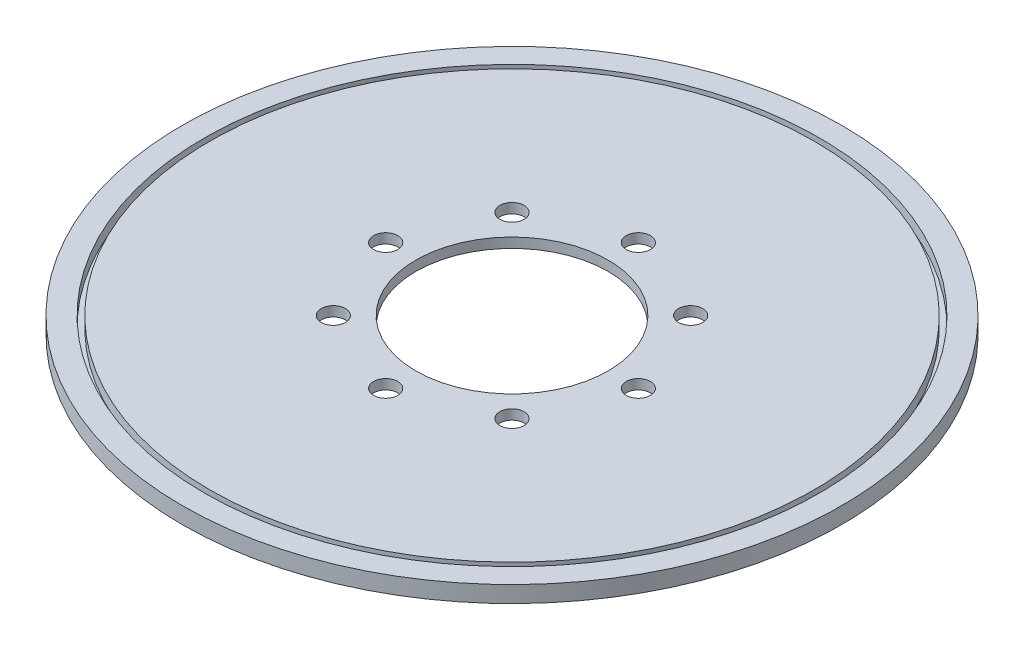
SolidWorks part; units mm, degrees
ref_plane "Front Plane" through (0, 0, 0) normal (0, 0, 1) x (1, 0, 0)
ref_plane "Top Plane" through (0, 0, 0) normal (0, 1, 0) x (1, 0, 0)
ref_plane "Right Plane" through (0, 0, 0) normal (1, 0, 0) x (0, 0, -1)
sketch "Sketch1" plane through (0, 0, 0) normal (0, 1, 0) x (1, 0, 0)
  circle A0 centre (0, 0) radius 300
  point P0 (0, 0)
  dimension "D1" = 600
extrude "plate" add sketch "Sketch1" along normal blind 15
sketch "Sketch2" plane through (0, 15, 0) normal (0, 1, 0) x (1, 0, 0)
  circle A0 centre (0, 0) radius 87.5
  dimension "D1" = 175
extrude "bearing-hole" cut sketch "Sketch2" against normal through all
sketch "Sketch4" plane through (0, 15, 0) normal (0, 1, 0) x (1, 0, 0)
  circle A0 centre (0, 0) radius 280
  circle A1 centre (0, 0) radius 275
  point P0 (0, 0)
  point P6 (0, 0)
  dimension "D1" = 560
  dimension "D2" = 550
extrude "Cut-Extrude3" cut sketch "Sketch4" against normal blind 10
sketch "Sketch5" plane through (0, 0, 0) normal (0, -1, 0) x (1, 0, 0)
  circle A0 centre (0, 0) radius 135
  dimension "D1" = 270
extrude "Cut-Extrude4" cut sketch "Sketch5" against normal blind 6
sketch "Sketch6" plane through (0, 6, 0) normal (0, -1, 0) x (1, 0, 0)
  circle A0 centre (0, 115) radius 6
  circle A1 centre (81.3173, 81.3173) radius 6
  circle A2 centre (115, 0) radius 6
  circle A3 centre (81.3173, -81.3173) radius 6
  circle A4 centre (0, -115) radius 6
  circle A5 centre (-81.3173, -81.3173) radius 6
  circle A6 centre (-115, 0) radius 6
  circle A7 centre (-81.3173, 81.3173) radius 6
  point P19 (0, 0)
  dimension "D1" = 12
  dimension "D2" = 115
  dimension "D3" = 8
extrude "Cut-Extrude5" cut sketch "Sketch6" against normal through all
sketch "Sketch7" plane through (0, 15, 0) normal (0, 1, 0) x (1, 0, 0)
  circle A0 centre (0, 115) radius 11
  circle A1 centre (81.3173, 81.3173) radius 11
  circle A2 centre (115, 0) radius 11
  circle A3 centre (81.3173, -81.3173) radius 11
  circle A4 centre (0, -115) radius 11
  circle A5 centre (-81.3173, -81.3173) radius 11
  circle A6 centre (-115, 0) radius 11
  circle A7 centre (-81.3173, 81.3173) radius 11
  point P19 (0, 0)
  dimension "D1" = 22
  dimension "D2" = 8
extrude "Cut-Extrude6" cut sketch "Sketch7" against normal blind 14
